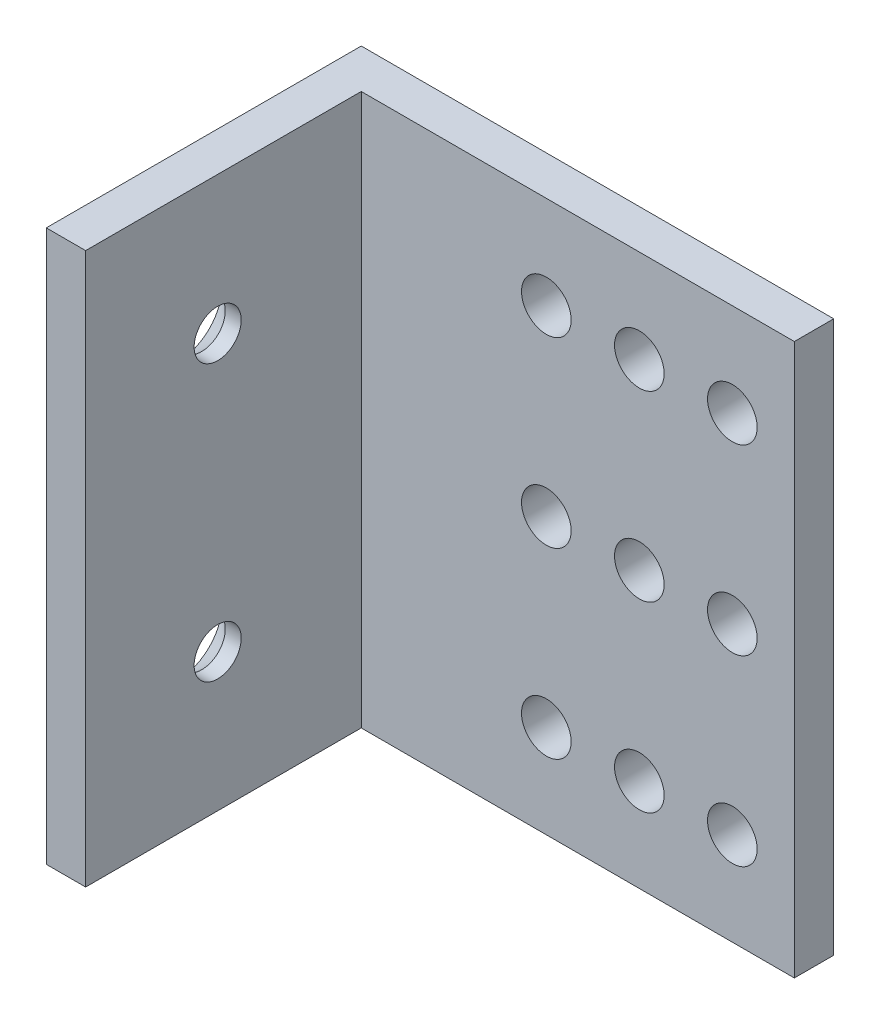
SolidWorks part; units mm, degrees
ref_plane "Front" through (0, 0, 0) normal (0, 0, 1) x (1, 0, 0)
ref_plane "Top" through (0, 0, 0) normal (0, 1, 0) x (1, 0, 0)
ref_plane "Right" through (0, 0, 0) normal (1, 0, 0) x (0, 0, -1)
sketch "Sketch1" plane through (0, 0, 0) normal (0, 1, 0) x (1, 0, 0)
  line L0 (-19.05, -12.7) -> (-15.875, -12.7)
  line L1 (-19.05, -12.7) -> (19.05, -12.7) construction
  line L2 (-19.05, -12.7) -> (-19.05, 12.7)
  line L3 (-19.05, 12.7) -> (19.05, 12.7)
  line L4 (19.05, -12.7) -> (19.05, 12.7) construction
  line L5 (-19.05, -12.7) -> (19.05, 12.7) construction
  line L6 (-19.05, 12.7) -> (19.05, -12.7) construction
  line L7 (-15.875, -12.7) -> (-15.875, 9.525)
  line L8 (-15.875, 9.525) -> (19.05, 9.525)
  line L9 (19.05, 9.525) -> (19.05, 12.7)
  point P0 (0, 0)
  point P10 (0, -12.7)
  dimension "D1" = 38.1
  dimension "D2" = 25.4
  dimension "D3" = 34.925
  dimension "D4" = 22.225
extrude "Boss-Extrude1" add sketch "Sketch1" along normal mid plane 44.45
sketch "Sketch2" plane through (-19.05, 0, 0) normal (-1, 0, 0) x (0, 0, 1)
  line L0 (-9.525, 22.225) -> (-9.525, -22.225) construction
  line L1 (-12.7, 22.225) -> (12.7, 22.225) construction
  line L2 (-12.7, -22.225) -> (12.7, -22.225) construction
  line L3 (12.7, 22.225) -> (12.7, -22.225) construction
  line L4 (-9.525, 22.225) -> (12.7, 22.225) construction
  line L5 (-9.525, 22.225) -> (-9.525, 0) construction
  line L6 (-9.525, 0) -> (12.7, 0) construction
  line L7 (12.7, 22.225) -> (12.7, 0) construction
  line L9 (-4.445, 22.225) -> (-4.445, -22.225) construction
  circle A0 centre (2.055, 11.1125) radius 2
  point P14 (12.7, 11.1125)
  dimension "D1" = 4
  dimension "D2" = 5.08
  dimension "D3" = 6.5
extrude "Cut-Extrude1" [suppressed] cut sketch "Sketch2" against normal through all
hole_wizard "CSK for #6 Flat Head Machine Screw1" positions "Sketch3" profile "Sketch5" countersink size "#6" standard "ANSI Inch" end condition through all
sketch "Sketch3" plane through (-19.05, 0, 0) normal (-1, 0, 0) x (0, 0, 1)
  point P0 (2.055, 11.1125)
sketch "Sketch5" plane through (-19.05, 11.1125, 2.055) normal (0, 1, 0) x (0, 0, 1)
  line L0 (0, 0) -> (0, 38.1)
  line L1 (0, 38.1) -> (1.8986, 38.1)
  line L2 (1.8986, 38.1) -> (1.8986, 1.892)
  line L3 (1.8986, 1.892) -> (3.5433, 0)
  line L5 (3.5433, 0) -> (0, 0)
  line L6 (-1.8986, 1.892) -> (-3.5433, 0) construction
  line L11 (0, -6.35) -> (0, 107.95) construction
  dimension "Thru Hole Dia." = 3.7973
  dimension "Thru Hole Depth" = 38.1
  dimension "Near C'Sink Dia." = 7.0866
  dimension "Near C'Sink Angle" = 82
sketch "Sketch6" plane through (0, 0, -12.7) normal (0, 0, -1) x (-1, 0, 0)
  line L0 (-19.05, 22.225) -> (-19.05, -22.225) construction
  line L1 (-19.05, -22.225) -> (19.05, -22.225) construction
  line L2 (-14.05, -14.725) -> (-6.55, -14.725) construction
  circle A0 centre (-14.05, -14.725) radius 2
  circle A1 centre (-6.55, -14.725) radius 2
  circle A2 centre (-6.55, 0) radius 2
  circle A3 centre (-6.55, 14.725) radius 2
  circle A4 centre (-14.05, 0) radius 2
  circle A5 centre (-14.05, 14.725) radius 2
  circle A6 centre (0.95, -14.725) radius 2
  circle A7 centre (0.95, 0) radius 2
  circle A8 centre (0.95, 14.725) radius 2
  point P7 (-14.05, 0)
  dimension "D4" = 4
  dimension "D1" = 5
  dimension "D2" = 7.5
  dimension "D3" = 14.725
  dimension "D8" = 7.5
  dimension "D5" = 3
  dimension "D6" = 3
extrude "Cut-Extrude2" cut sketch "Sketch6" against normal through all
mirror "Mirror1" about plane through (0, 0, 0) normal (0, 1, 0) of "CSK for #6 Flat Head Machine Screw1"
